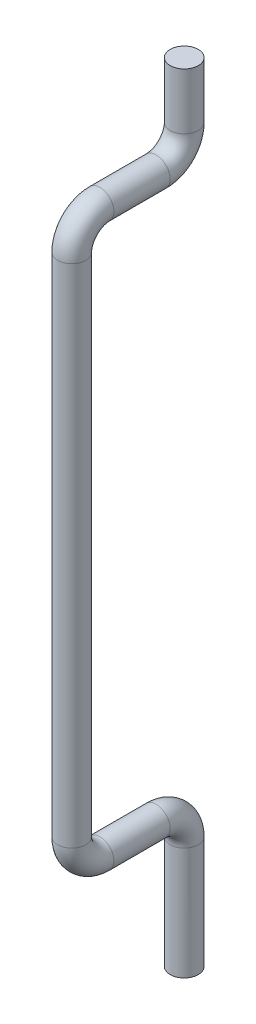
SolidWorks part; units mm, degrees
ref_plane "Front Plane" through (0, 0, 0) normal (0, 0, 1) x (1, 0, 0)
ref_plane "Top Plane" through (0, 0, 0) normal (0, 1, 0) x (1, 0, 0)
ref_plane "Right Plane" through (0, 0, 0) normal (1, 0, 0) x (0, 0, -1)
sketch "Sketch1" plane through (0, 0, 0) normal (1, 0, 0) x (0, 0, -1)
  line L0 (10.22, 3) -> (12.22, 3)
  line L1 (13.22, 2) -> (13.22, -2)
  line L2 (9.22, 4) -> (9.22, 22)
  line L3 (10.22, 23) -> (12.22, 23)
  line L4 (13.22, 24) -> (13.22, 26)
  arc A0 (12.22, 3) -> (13.22, 2) centre (12.22, 2) cw
  arc A1 (9.22, 4) -> (10.22, 3) centre (10.22, 4) ccw
  arc A3 (9.22, 22) -> (10.22, 23) centre (10.22, 22) cw
  arc A4 (12.22, 23) -> (13.22, 24) centre (12.22, 24) ccw
  point P9 (13.22, 3)
  point P19 (9.22, 23)
  point P22 (13.22, 23)
  dimension "D8" = 1
  dimension "D9" = 1
  dimension "D5" = 1
  dimension "D1" = 3
  dimension "D2" = 4
  dimension "D3" = 20
  dimension "D4" = 5
ref_plane "Plane1" through (0, -2, 0) normal (0, 1, 0) x (1, 0, 0)
sketch "Sketch2" plane through (0, -2, 0) normal (0, 1, 0) x (1, 0, 0)
  circle A0 centre (0, 13.22) radius 0.5
  dimension "D1" = 1
sweep "Sweep1" add profiles "Sketch2" path "Sketch1"
